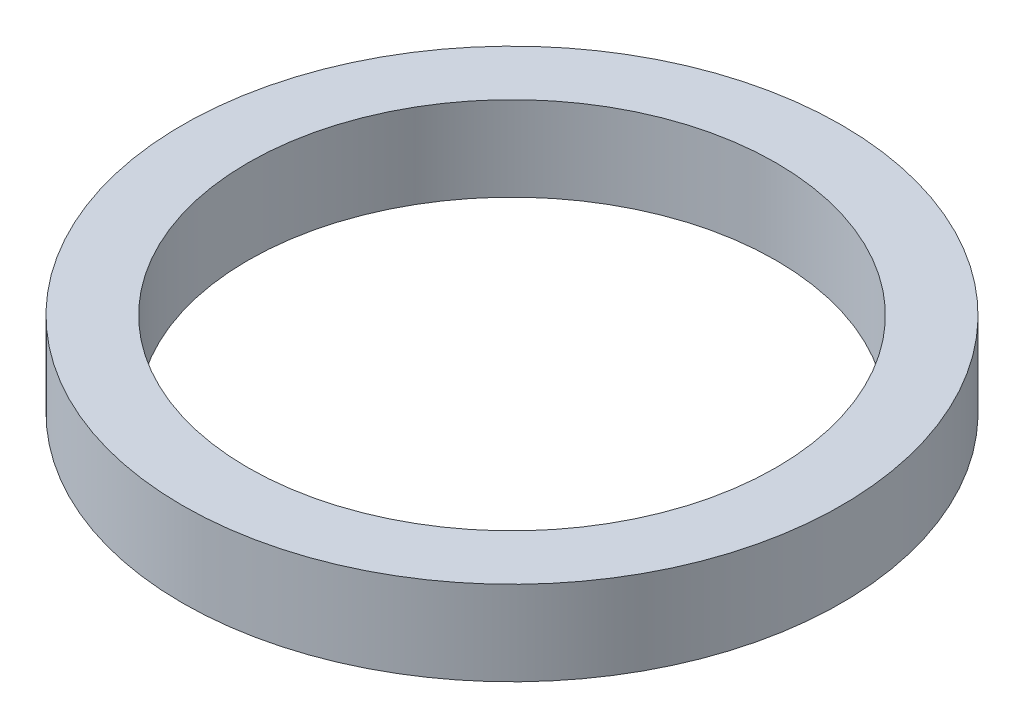
SolidWorks part; units mm, degrees
ref_plane "Front Plane" through (0, 0, 0) normal (0, 0, 1) x (1, 0, 0)
ref_plane "Top Plane" through (0, 0, 0) normal (0, 1, 0) x (1, 0, 0)
ref_plane "Right Plane" through (0, 0, 0) normal (1, 0, 0) x (0, 0, -1)
sketch "Sketch2" plane through (0, 0, 0) normal (0, 1, 0) x (1, 0, 0)
  circle A0 centre (0, 0) radius 49.55
  circle A1 centre (0, 0) radius 39.7
  dimension "D1" = 99.1
  dimension "D2" = 79.4
extrude "Boss-Extrude1" add sketch "Sketch2" along normal blind 12.7
